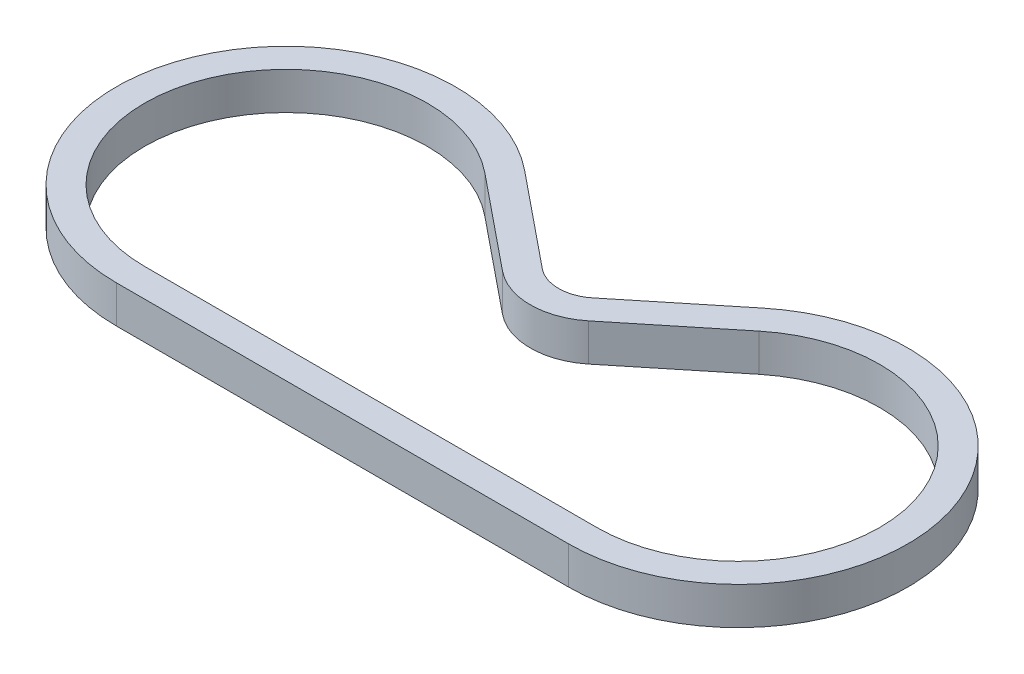
SolidWorks part; units mm, degrees
material "6061 Alloy"
ref_plane "Front Plane" through (0, 0, 0) normal (0, 0, 1) x (1, 0, 0)
ref_plane "Top Plane" through (0, 0, 0) normal (0, 1, 0) x (1, 0, 0)
ref_plane "Right Plane" through (0, 0, 0) normal (1, 0, 0) x (0, 0, -1)
sketch "Sketch1" plane through (0, 0, 0) normal (0, 1, 0) x (1, 0, 0)
  line L0 (-47.1, 0) -> (47.1, 0) construction
  line L1 (-47.1, 0) -> (47.1, 0) construction
  line L3 (-47.1, -35.3387) -> (47.1, -35.3387)
  line L4 (-47.1, 0) -> (47.1, 0) construction
  line L6 (-47.1, -29.4459) -> (47.1, -29.4459)
  line L7 (-47.1, 29.4459) -> (-47.1, 35.3387) construction
  line L8 (0, 0) -> (0, 18) construction
  line L9 (-26.6827, 25.1475) -> (-7.1033, 9.251) construction
  line L10 (-28.5399, 22.8601) -> (-8.9605, 6.9636)
  line L11 (-24.8256, 27.4349) -> (-5.2462, 11.5384)
  line L12 (28.5399, 22.8601) -> (8.9605, 6.9636)
  line L13 (24.8256, 27.4349) -> (5.2462, 11.5384)
  line L14 (-8.9605, 6.9636) -> (-5.2462, 11.5384) construction
  arc A0 (-47.1, 35.3387) -> (-47.1, -35.3387) centre (-47.1, 0) ccw
  arc A1 (47.1, -35.3387) -> (47.1, 35.3387) centre (47.1, 0) ccw
  arc A2 (-47.1, 29.4459) -> (-47.1, -29.4459) centre (-47.1, 0) ccw
  arc A3 (47.1, -29.4459) -> (47.1, 29.4459) centre (47.1, 0) ccw
  arc A4 (-7.1033, 9.251) -> (7.1033, 9.251) centre (0, 18) ccw construction
  arc A5 (-28.5399, 22.8601) -> (-47.1, 29.4459) centre (-47.1, 0) ccw
  arc A7 (-8.9605, 6.9636) -> (8.9605, 6.9636) centre (0, 18) ccw
  arc A9 (-5.2462, 11.5384) -> (5.2462, 11.5384) centre (0, 18) ccw
  arc A10 (-7.1033, 9.251) -> (7.1787, 9.3127) centre (0, 18) ccw construction
  arc A11 (-8.9605, 6.9636) -> (9.0556, 7.0415) centre (0, 18) ccw construction
  arc A12 (-5.2462, 11.5384) -> (5.3019, 11.584) centre (0, 18) ccw construction
  arc A13 (28.5399, 22.8601) -> (47.1, 29.4459) centre (47.1, 0) cw
  arc A14 (24.8256, 27.4349) -> (47.1, 35.3387) centre (47.1, 0) cw
  arc A15 (-47.1, 29.4459) -> (-28.5399, 22.8601) centre (-47.1, 0) cw construction
  arc A16 (-47.1, 35.3387) -> (-24.8256, 27.4349) centre (-47.1, 0) cw construction
  arc A17 (-47.1, 32.3923) -> (-26.6827, 25.1475) centre (-47.1, 0) cw construction
  arc A18 (-24.8256, 27.4349) -> (-47.1, 35.3387) centre (-47.1, 0) ccw
  point P0 (0, 0)
  point P4 (0, 0)
  point P10 (0, 0)
  point P13 (-9.1, 6.9636)
  point P17 (-8.7267, 6.9636)
  point P18 (-47.1, 32.3923)
  point P28 (-5.2462, 11.5384)
  point P40 (-7.1033, 9.251)
  point P42 (-8.9605, 6.9636)
  point P43 (-5.2462, 11.5384)
  dimension "D2" = 32.3923
  dimension "D3" = 5.8928
  dimension "D4" = 11.2696
  dimension "D1" = 94.2
  dimension "D5" = 18
extrude "Boss-Extrude1" add sketch "Sketch1" along normal blind 7.7978 contours A14 L13 A9 L11 A0 L3 A1 L12 A13 A3 L6 A2 L10 A7 region at (-80.6448, 0, 0)
